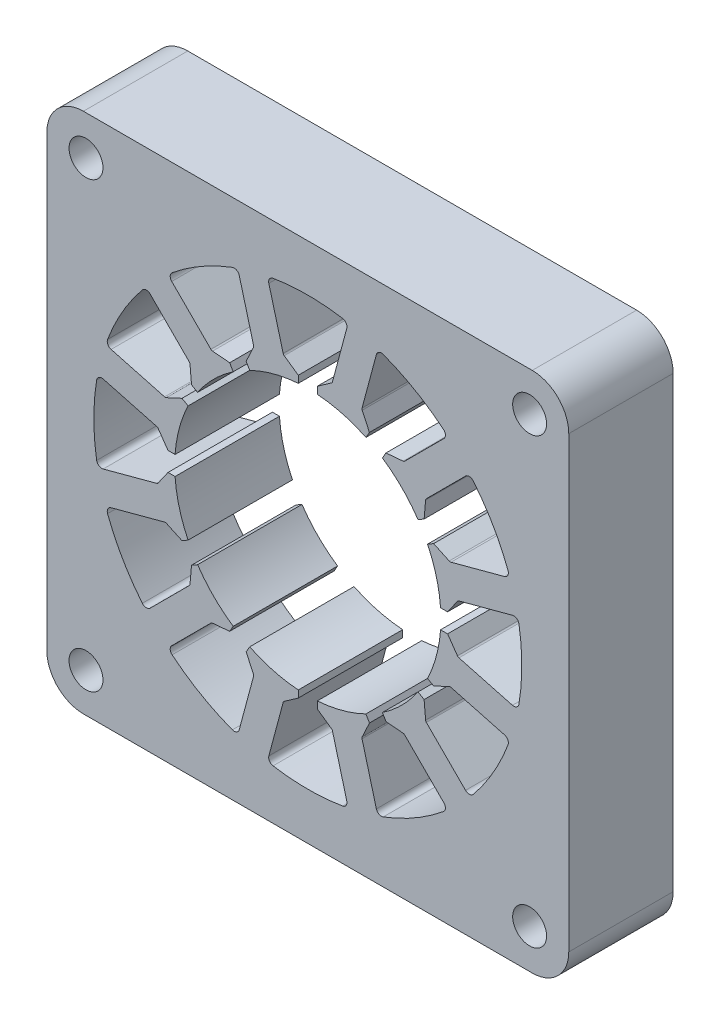
SolidWorks part; units mm, degrees
ref_plane "Front" through (0, 0, 0) normal (0, 0, 1) x (1, 0, 0)
ref_plane "Top" through (0, 0, 0) normal (0, 1, 0) x (1, 0, 0)
ref_plane "Right" through (0, 0, 0) normal (1, 0, 0) x (0, 0, -1)
sketch "Sketch1" plane through (0, 0, 0) normal (0, 0, 1) x (1, 0, 0)
  line L1 (-50, 50) -> (50, 50)
  line L2 (-50, 50) -> (-50, -50)
  line L3 (-50, -50) -> (50, -50)
  line L4 (50, 50) -> (50, -50)
  circle A0 centre (0, 0) radius 50 construction
  circle A1 centre (0, 0) radius 25.5
  dimension "D1" = 100
  dimension "D2" = 51
extrude "Lamination Extruction" add sketch "Sketch1" along normal blind 20
ref_axis "Axis1" through (0, 0, 20) along (0, 0, -1)
sketch "Sketch2" plane through (0, 0, 20) normal (0, 0, 1) x (1, 0, 0)
  line L0 (0, 0) -> (0, 50) construction
  line L1 (50, 50) -> (-50, 50) construction
  line L2 (-1.825, 26.7846) -> (1.825, 26.7846) construction
  line L3 (7.75, 40.2609) -> (4.6735, 28.7791)
  line L4 (4.6735, 28.7791) -> (1.825, 26.7846)
  line L5 (-1.825, 26.7846) -> (-1.825, 25.4346)
  line L6 (-7.75, 40.2609) -> (-4.6735, 28.7791)
  line L7 (-4.6735, 28.7791) -> (-1.825, 26.7846)
  line L8 (1.825, 26.7846) -> (1.825, 25.4346)
  line L9 (-4.6735, 28.7791) -> (4.6735, 28.7791) construction
  arc A1 (-7.75, 40.2609) -> (7.75, 40.2609) centre (0, 0) cw
  circle A3 centre (0, 0) radius 25.5 construction
  arc A4 (1.825, 25.4346) -> (-1.825, 25.4346) centre (0, 0) ccw
  point P7 (0, 26.7846)
  point P16 (0, 41)
  point P19 (0, 28.7791)
  circle M15 centre (0, 0) radius 25.5
  dimension "D2" = 41
  dimension "D1" = 30
  dimension "D3" = 15.5
  dimension "D6" = 35
  dimension "D4" = 1.35
  dimension "D5" = 3.65
extrude "Slot Cut" cut sketch "Sketch2" against normal through all contours A1 L6 L7 L5 L8 L4 L3 M15 region at (0, 34.4506, 20)
fillet "Slot Fillet Top" radius 1 2 edges at (7.75, 40.2609, 10) (-7.75, 40.2609, 10)
fillet "Slot Fillet Bottom" radius 0.5 2 edges at (4.6735, 28.7791, 10) (-4.6735, 28.7791, 10)
pattern_circular "Slot Duplicate" count 12 over 360 about axis through (0, 0, 20) along (0, 0, -1) of "Slot Cut", "Slot Fillet Top", "Slot Fillet Bottom"
sketch "Sketch3" plane through (0, 0, 20) normal (0, 0, 1) x (1, 0, 0)
  line L1 (42.5, 42.5) -> (-42.5, 42.5) construction
  line L2 (42.5, 42.5) -> (42.5, -42.5) construction
  line L3 (42.5, -42.5) -> (-42.5, -42.5) construction
  line L4 (-42.5, 42.5) -> (-42.5, -42.5) construction
  line L5 (42.5, 42.5) -> (-42.5, -42.5) construction
  line L6 (42.5, -42.5) -> (-42.5, 42.5) construction
  circle A1 centre (-42.5, 42.5) radius 3.25
  circle A2 centre (42.5, 42.5) radius 3.25
  circle A3 centre (42.5, -42.5) radius 3.25
  circle A4 centre (-42.5, -42.5) radius 3.25
  point P0 (0, 0)
  dimension "D2" = 6.5
  dimension "D1" = 85
extrude "Bolt Hole Cut" cut sketch "Sketch3" against normal through all
fillet "Corner Fillet" radius 7 4 edges at (-50, 50, 10) (-50, -50, 10) (50, -50, 10) (50, 50, 10)
equation "\"DS1\"= 100mm"
equation "\"D1@Sketch1\"=\"DS1\""
equation "\"DS2\"=51"
equation "\"D2@Sketch1\"=\"DS2\""
equation "\"HEIGHT\"=20"
equation "\"D1@Lamination Extruction\"=\"HEIGHT\""
equation "\"AngSlot\"=30"
equation "\"D1@Sketch2\"=\"AngSlot\""
equation "\"DSS\"= 15.5mm"
equation "\"D2@Sketch2\"=\"DSS\"+\"DS2\"/2"
equation "\"WSSB\"=15.5"
equation "\"D3@Sketch2\"=\"WSSB\""
equation "\"WSSO\"=3.65"
equation "\"HSTT\"=1.35"
equation "\"AngSTT\"=35"
equation "\"D6@Sketch2\"=\"AngSTT\""
equation "\"D4@Sketch2\"=\"HSTT\""
equation "\"D5@Sketch2\"=\"WSSO\""
equation "\"FRSSB\"=1"
equation "\"D1@Slot Fillet Top\" = \"FRSSB\""
equation "\"FRSST\"=0.5"
equation "\"D1@Slot Fillet Bottom\" = \"FRSST\""
equation "\"SLOTS\"=12"
equation "\"D1@Slot Duplicate\" = \"SLOTS\""
equation "\"HOLE_BOLT\"= 85"
equation "\"D1@Sketch3\"=\"HOLE_BOLT\""
equation "\"BOLT_DIA\"=6.5"
equation "\"D2@Sketch3\"=\"BOLT_DIA\""
equation "\"LAM_FILLET\"=7"
equation "\"D1@Corner Fillet\"=\"LAM_FILLET\""
